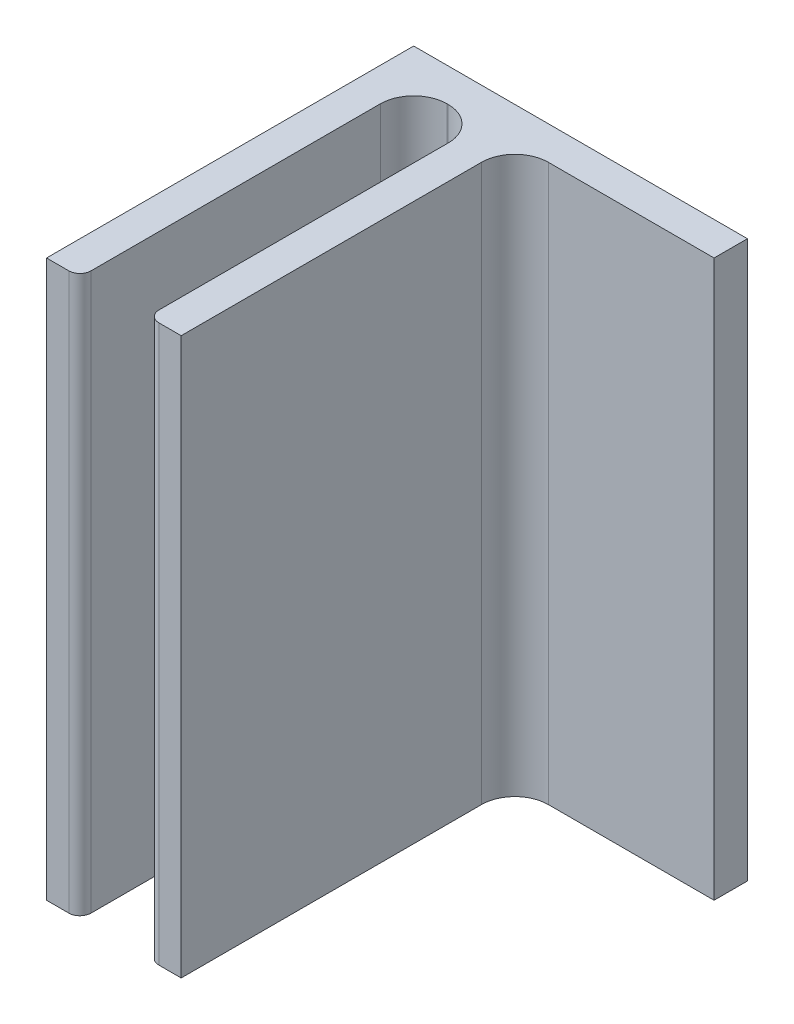
SolidWorks part; units mm, degrees
ref_plane "Front" through (0, 0, 0) normal (0, 0, 1) x (1, 0, 0)
ref_plane "Top" through (0, 0, 0) normal (0, 1, 0) x (1, 0, 0)
ref_plane "Right" through (0, 0, 0) normal (1, 0, 0) x (0, 0, -1)
sketch "Sketch1" plane through (0, 0, 0) normal (0, 0, 1) x (1, 0, 0)
  line L5 (0, 0) -> (30, 0)
  line L6 (0, 0) -> (0, 50)
  line L7 (0, 50) -> (30, 50)
  line L8 (30, 0) -> (30, 50)
  dimension "D1" = 50
  dimension "D2" = 30
extrude "Boss-Extrude1" add sketch "Sketch1" along normal blind 3
sketch "Sketch2" plane through (0, 0, 3) normal (0, 0, 1) x (1, 0, 0)
  line L0 (0, 0) -> (30, 0) construction
  line L1 (0, 50) -> (3, 50)
  line L2 (0, 50) -> (0, 0)
  line L3 (0, 0) -> (3, 0)
  line L4 (3, 50) -> (3, 0)
  line L10 (30, 50) -> (0, 50) construction
  line L11 (9.1, 50) -> (12.1, 50)
  line L12 (9.1, 50) -> (9.1, 0)
  line L13 (9.1, 0) -> (12.1, 0)
  line L14 (12.1, 50) -> (12.1, 0)
  dimension "D1" = 3
  dimension "D2" = 6.1
extrude "Boss-Extrude2" add sketch "Sketch2" along normal blind 30
fillet "Fillet2" radius 3 3 edges at (12.1, 25, 3) (3, 25, 3) (9.1, 25, 3)
fillet "Fillet3" radius 1 2 edges at (9.1, 25, 33) (3, 25, 33)
